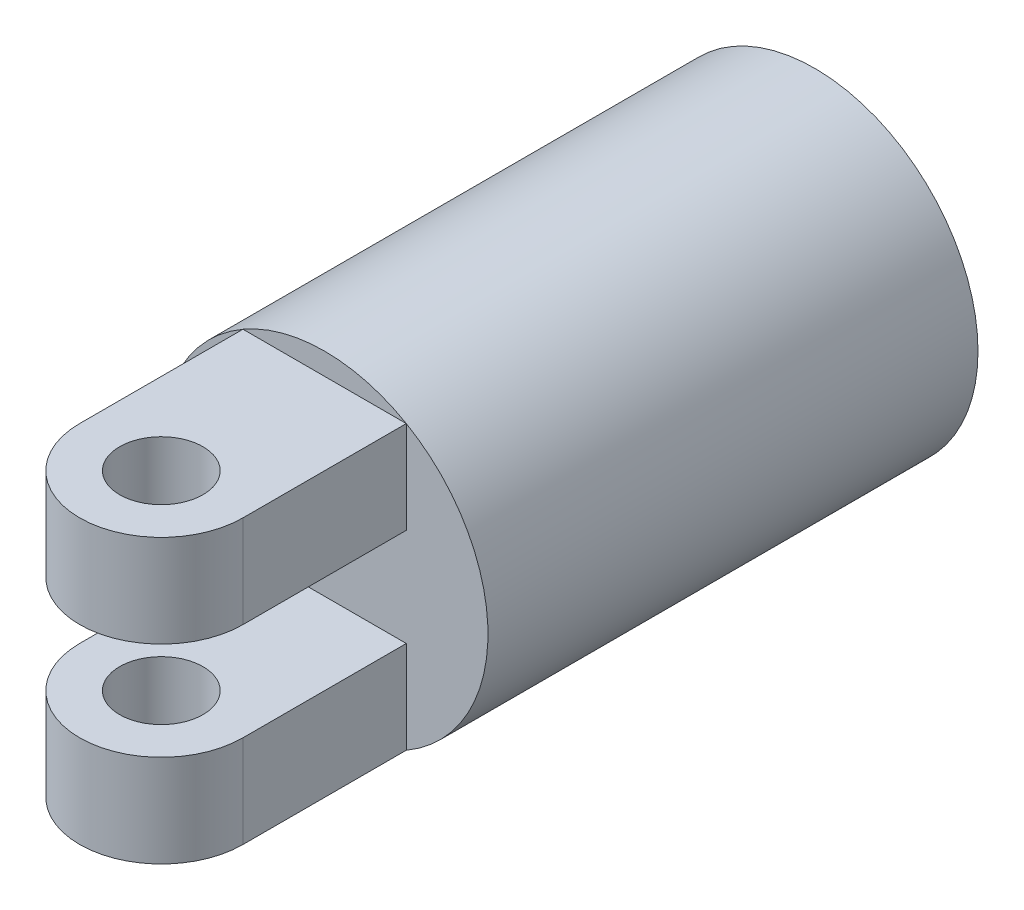
SolidWorks part; units mm, degrees
material "ABS"
ref_plane "Спереди" through (0, 0, 0) normal (0, 0, 1) x (1, 0, 0)
ref_plane "Сверху" through (0, 0, 0) normal (0, 1, 0) x (1, 0, 0)
ref_plane "Справа" through (0, 0, 0) normal (1, 0, 0) x (0, 0, -1)
sketch "Эскиз1" plane through (0, 0, 0) normal (0, 0, 1) x (1, 0, 0)
  line L0 (0, 0) -> (0, 17.8502) construction
  line L1 (0, 17.8502) -> (0, 35.1935) construction
  line L2 (-32.8267, 17.8502) -> (30.9899, 17.8502) construction
  circle A0 centre (0, 17.8502) radius 10
  circle A1 centre (0, 17.8502) radius 5
  circle A2 centre (0, 17.8502) radius 5
  circle A3 centre (0, 17.8502) radius 5
extrude "Бобышка-Вытянуть1" add sketch "Эскиз1" along normal blind 30 contours A0 | A0 region at (-9.7172, 17.8502, 0)
sketch "Эскиз2" plane through (0, 0, 30) normal (0, 0, 1) x (1, 0, 0)
  line L0 (-5.0009, 26.5099) -> (5.0009, 9.1904) construction
  line L5 (0, 17.8502) -> (-8.6597, 12.8493) construction
  line L6 (0, 17.8502) -> (8.6597, 22.8511) construction
  line L8 (-5, 26.5104) -> (5, 26.5104)
  line L9 (-5, 26.5104) -> (-5, 9.1899)
  line L10 (-5, 9.1899) -> (5, 9.1899)
  line L11 (5, 26.5104) -> (5, 9.1899)
  line L12 (-5, 26.5104) -> (5, 9.1899) construction
  line L13 (-5, 9.1899) -> (5, 26.5104) construction
  circle A1 centre (0, 17.8502) radius 10 construction
  dimension "D1" = 10
extrude "Бобышка-Вытянуть3" add sketch "Эскиз2" along normal blind 15 contours L9 L8 L11 L10
sketch "Эскиз5" plane through (0, 26.5104, 0) normal (0, 1, 0) x (1, 0, 0)
  line L0 (0, -45) -> (0, -30) construction
  line L1 (-5, -45) -> (5, -45) construction
  line L2 (-5, -30) -> (5, -30) construction
  line L3 (5, -45) -> (5, -30) construction
  line L4 (5, -37.5) -> (-5, -37.5) construction
  line L5 (-5, -45) -> (-5, -30) construction
  line L6 (5, -40) -> (5, -45)
  line L7 (5, -45) -> (0, -45)
  line L8 (0, -45) -> (-5, -45)
  line L9 (-5, -45) -> (-5, -40)
  line L10 (-5, -40) -> (5, -40) construction
  circle A0 centre (0, -40) radius 5
  circle A1 centre (0, -40) radius 2.55
  line M3 (-5, -30) -> (-5, -45)
  line M4 (-5, -45) -> (5, -45)
  line M5 (5, -45) -> (5, -30)
  dimension "D1" = 5.1
extrude "Вырез-Вытянуть1" cut sketch "Эскиз5" against normal through all contours A0 M4 M5 region at (3.8832, 26.5104, 43.8832)
extrude "Вырез-Вытянуть2" cut sketch "Эскиз5<3>" against normal through all contours A0 M3 M4 region at (-3.8832, 26.5104, 43.8832)
sketch "Эскиз5<3>" plane through (0, 26.5104, 0) normal (0, 1, 0) x (1, 0, 0) same geometry as "Эскиз5"
sketch "Эскиз6" plane through (5, 0, 0) normal (1, 0, 0) x (0, 0, -1)
  line L0 (-30, 17.8502) -> (-40, 17.8502) construction
  line L1 (-30, 26.5104) -> (-30, 9.1899) construction
  line L2 (-40, 9.1899) -> (-40, 26.5104) construction
  line L3 (-35, 26.5104) -> (-35, 9.1899) construction
  line L4 (-40, 26.5104) -> (-30, 26.5104) construction
  line L5 (-40, 9.1899) -> (-30, 9.1899) construction
  line L6 (-40, 14.8502) -> (-47.356, 14.8502)
  line L7 (-30, 14.8502) -> (-40, 14.8502)
  line L8 (-30, 14.8502) -> (-30, 20.8502)
  line L9 (-30, 20.8502) -> (-40, 20.8502)
  line L11 (-30, 14.8502) -> (-40, 20.8502) construction
  line L12 (-30, 20.8502) -> (-40, 14.8502) construction
  line L13 (-47.356, 14.8502) -> (-47.356, 20.8502)
  line L14 (-47.356, 20.8502) -> (-40, 20.8502)
  point P12 (-35, 17.8502)
  dimension "D1" = 6
extrude "Вырез-Вытянуть3" cut sketch "Эскиз6" against normal blind 15
extrude "Вырез-Вытянуть4" cut sketch "Эскиз5<4>" against normal through all contours A1 region at (0, 26.5104, 40)
sketch "Эскиз5<4>" plane through (0, 26.5104, 0) normal (0, 1, 0) x (1, 0, 0) same geometry as "Эскиз5"
sketch "Эскиз8" plane through (0, 0, 0) normal (0, 0, -1) x (-1, 0, 0)
sketch "Эскиз9" plane through (0, 0, 0) normal (0, 0, -1) x (-1, 0, 0)
  circle A0 centre (0, 17.8502) radius 5.05
  dimension "D1" = 10.1
extrude "Вырез-Вытянуть5" cut sketch "Эскиз9" against normal blind 25
